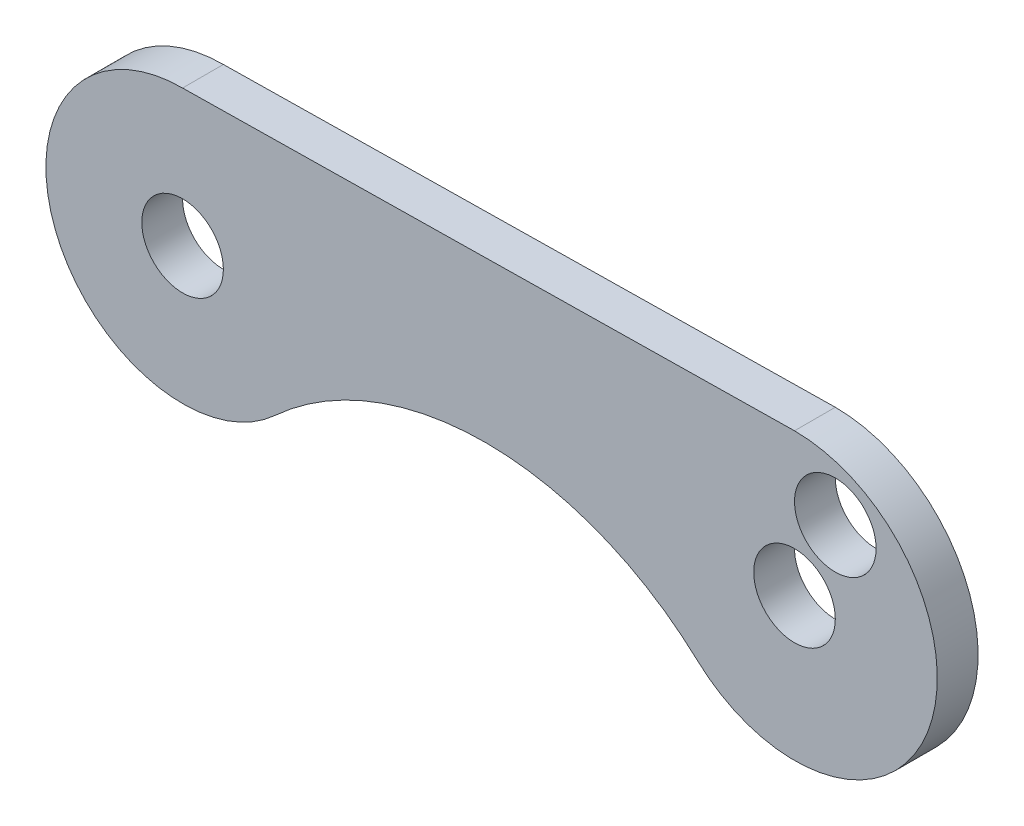
SolidWorks part; units mm, degrees
ref_plane "Front Plane" through (0, 0, 0) normal (0, 0, 1) x (1, 0, 0)
ref_plane "Top Plane" through (0, 0, 0) normal (0, 1, 0) x (1, 0, 0)
ref_plane "Right Plane" through (0, 0, 0) normal (1, 0, 0) x (0, 0, -1)
sketch "Sketch1" plane through (0, 0, 0) normal (0, 0, 1) x (1, 0, 0)
  line L0 (-31.0207, 6.8289) -> (-1.0207, 7.2757)
  arc A0 (-31.0207, 6.8289) -> (-26.4957, -4.8122) centre (-31.0207, 0.1289) ccw
  arc A1 (-5.7737, -4.8633) -> (-1.2292, 7.2726) centre (-1.0207, 0.2757) ccw
  arc A2 (-5.7737, -4.8633) -> (-26.4957, -4.8122) centre (-16.1624, -16.0955) ccw
  circle A3 centre (-31.0207, 0.1289) radius 2
  circle A4 centre (-1.0207, 0.2757) radius 2
  circle A5 centre (0.9793, 4.2757) radius 2
  dimension "D1" = 30
  dimension "D2" = 14
  dimension "D3" = 13.4
  dimension "D5" = 4
  dimension "D6" = 4
  dimension "D7" = 4
  dimension "D4" = 2
  dimension "D8" = 4
extrude "Boss-Extrude1" add sketch "Sketch1" along normal blind 2 contours A2 A1 L0 A0 A5 A4 A3 region at (-16.1072, 1.1568, 0)
